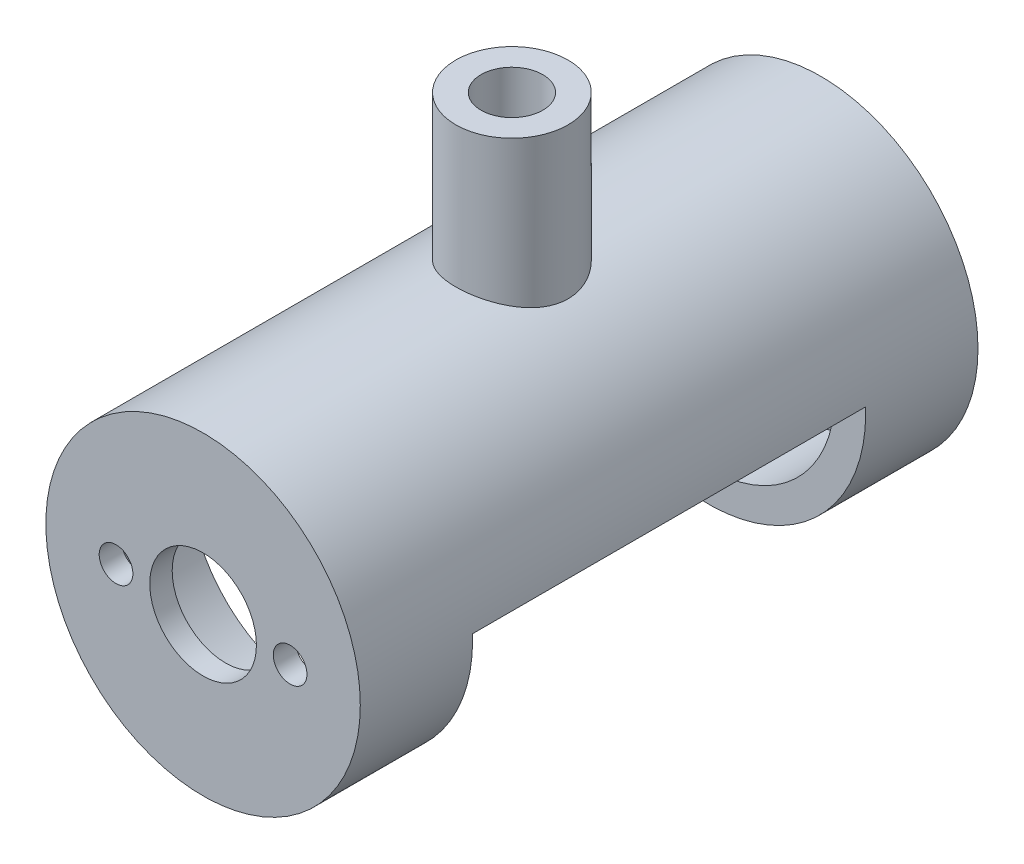
SolidWorks part; units mm, degrees
ref_plane "Alzado" through (0, 0, 0) normal (0, 0, 1) x (1, 0, 0)
ref_plane "Planta" through (0, 0, 0) normal (0, 1, 0) x (1, 0, 0)
ref_plane "Vista lateral" through (0, 0, 0) normal (1, 0, 0) x (0, 0, -1)
sketch "Croquis7" plane through (0, 0, 0) normal (0, 1, 0) x (1, 0, 0)
  circle A0 centre (0, 0) radius 5
  circle A1 centre (0, 0) radius 2.5
  dimension "D1" = 5
  dimension "D2" = 10
extrude "Saliente-Extruir7" add sketch "Croquis7" along normal blind 13
sketch "Croquis8" plane through (0, 0, 0) normal (0, 0, 1) x (1, 0, 0)
  circle A0 centre (0, -6.5) radius 6.5
  circle A1 centre (0, -6.5) radius 4
  dimension "D1" = 6.5
  dimension "D2" = 8
extrude "Saliente-Extruir8" add sketch "Croquis8" against normal blind 20 and the other way blind 20 separate body
sketch "Croquis9" plane through (0, 13, 0) normal (0, 1, 0) x (1, 0, 0)
  circle A0 centre (0, 0) radius 5
  circle A1 centre (0, 0) radius 2.5
extrude "Saliente-Extruir10" add sketch "Croquis9" against normal blind 16
sketch "Croquis10" plane through (0, 0, 20) normal (0, 0, 1) x (1, 0, 0)
  circle A0 centre (0, -6.5) radius 4
extrude "Cortar-Extruir1" cut sketch "Croquis10" against normal blind 43
sketch "Croquis11" plane through (0, 0, 20) normal (0, 0, 1) x (1, 0, 0)
  line L1 (-1, -9.2127) -> (1, -9.2127)
  line L2 (-1, -9.2127) -> (-1, -14.2827)
  line L3 (-1, -14.2827) -> (1, -14.2827)
  line L4 (1, -9.2127) -> (1, -14.2827)
  line L5 (-1, -9.2127) -> (1, -14.2827) construction
  line L6 (-1, -14.2827) -> (1, -9.2127) construction
  point P0 (0, -11.7477)
extrude "Cortar-Extruir2" cut sketch "Croquis11" against normal blind 43
sketch "Croquis12" plane through (0, 0, -20) normal (0, 0, -1) x (-1, 0, 0)
  line L1 (-1, -10.373) -> (-3.5, -10.373)
  line L2 (-1, -10.373) -> (-1, -18.923)
  line L3 (-1, -18.923) -> (-3.5, -18.923)
  line L4 (-3.5, -10.373) -> (-3.5, -18.923)
  dimension "D1" = 2.5
  dimension "D2" = 8.55
extrude "Saliente-Extruir11" add sketch "Croquis12" against normal blind 40
sketch "Croquis13" plane through (0, 0, -20) normal (0, 0, -1) x (-1, 0, 0)
  line L1 (1, -10.373) -> (3.5, -10.373)
  line L2 (1, -10.373) -> (1, -18.923)
  line L3 (1, -18.923) -> (3.5, -18.923)
  line L4 (3.5, -10.373) -> (3.5, -18.923)
  dimension "D1" = 2.5
  dimension "D2" = 8.55
extrude "Saliente-Extruir12" add sketch "Croquis13" against normal blind 40
sketch "Croquis14" plane through (-3.5, 0, 0) normal (-1, 0, 0) x (0, 0, 1)
  line L0 (-20, -18.923) -> (-20, -11.9772) construction
  line L1 (20, -18.923) -> (20, -11.9772) construction
  circle A0 centre (-13, -15.4501) radius 1.5
  circle A1 centre (0, -15.4501) radius 1.5
  circle A2 centre (13, -15.4501) radius 1.5
  dimension "D1" = 7
  dimension "D2" = 7
extrude "Cortar-Extruir3" cut sketch "Croquis14" against normal blind 40
sketch "Croquis15" plane through (0, 0, 20) normal (0, 0, 1) x (1, 0, 0)
  line L1 (-15.4538, 0) -> (9.6496, 0)
  line L2 (-15.4538, 0) -> (-15.4538, -20.0115)
  line L3 (-15.4538, -20.0115) -> (9.6496, -20.0115)
  line L4 (9.6496, 0) -> (9.6496, -20.0115)
extrude "Cortar-Extruir4" cut sketch "Croquis15" against normal blind 40
sketch "Croquis16" plane through (0, 0, 0) normal (0, 0, 1) x (1, 0, 0)
  line L0 (-5, 0) -> (5, 0) construction
  circle A0 centre (0, -13.5) radius 13.5
  circle A1 centre (0, -13.5) radius 11
  dimension "D1" = 13.5
extrude "Saliente-Extruir14" add sketch "Croquis16" against normal blind 55 and the other way blind 55 separate body
sketch "Croquis17" plane through (0, 13, 0) normal (0, 1, 0) x (1, 0, 0)
  circle A0 centre (0, 0) radius 2.5
  circle A1 centre (0, 0) radius 5
extrude "Saliente-Extruir15" add sketch "Croquis17" against normal blind 15
sketch "Croquis18" plane through (0, 0, -55) normal (0, 0, -1) x (-1, 0, 0)
  circle A0 centre (0, -13.5) radius 11
  circle A1 centre (0, -13.5) radius 4.25
extrude "Saliente-Extruir16" add sketch "Croquis18" against normal blind 3
sketch "Croquis20" plane through (0, 0, -55) normal (0, 0, -1) x (-1, 0, 0)
  circle A0 centre (-7.75, -13.5) radius 1.5
  circle A1 centre (7.75, -13.5) radius 1.5
  circle A2 centre (0, -13.5) radius 4.25 construction
  dimension "D1" = 7.75
  dimension "D2" = 7.75
extrude "Cortar-Extruir5" cut sketch "Croquis20" against normal blind 3
sketch "Croquis21" plane through (0, 0, 55) normal (0, 0, 1) x (1, 0, 0)
  circle A0 centre (0, -13.5) radius 11
  circle A1 centre (0, -13.5) radius 4.25
  circle A2 centre (7.75, -13.5) radius 1.5
  circle A3 centre (-7.75, -13.5) radius 1.3863
extrude "Saliente-Extruir17" add sketch "Croquis21" against normal blind 3
sketch "Croquis22" plane through (0, 0, 0) normal (1, 0, 0) x (0, 0, -1)
  line L0 (-55, -27) -> (55, -27) construction
  line L1 (-45, -27) -> (45, -27)
  line L2 (-45, -27) -> (-45, -13)
  line L3 (-45, -13) -> (45, -13)
  line L4 (45, -27) -> (45, -13)
  line L5 (-55, 0) -> (-55, -27) construction
  line L6 (55, -27) -> (55, 0) construction
  dimension "D1" = 10
  dimension "D2" = 10
  dimension "D3" = 14
extrude "Cortar-Extruir6" cut sketch "Croquis22" against normal blind 18 and the other way blind 31
sketch "Croquis24" plane through (0, 0, 55) normal (0, 0, 1) x (1, 0, 0)
  circle A0 centre (0, -13.5) radius 13.5
extrude "Cortar-Extruir7" cut sketch "Croquis24" against normal blind 27.5
sketch "Croquis27" plane through (0, 0, 27.5) normal (0, 0, 1) x (1, 0, 0)
  circle A0 centre (0, -13.5) radius 13.5
  circle A1 centre (0, -13.5) radius 11
extrude "Saliente-Extruir19" add sketch "Croquis27" against normal blind 10
sketch "Croquis28" plane through (0, 0, 27.5) normal (0, 0, 1) x (1, 0, 0)
  circle A0 centre (0, -13.5) radius 11
  circle A1 centre (-7.75, -13.5) radius 1.5
  circle A2 centre (7.75, -13.5) radius 1.5
  circle A3 centre (0, -13.5) radius 4.25
extrude "Saliente-Extruir20" add sketch "Croquis28" against normal blind 3
sketch "Croquis29" plane through (0, 0, -55) normal (0, 0, -1) x (-1, 0, 0)
  circle A0 centre (0, -13.5) radius 13.5
extrude "Cortar-Extruir8" cut sketch "Croquis29" against normal blind 27.5
sketch "Croquis30" plane through (0, 0, -27.5) normal (0, 0, -1) x (-1, 0, 0)
  circle A0 centre (0, -13.5) radius 13.5
  circle A1 centre (0, -13.5) radius 11
extrude "Saliente-Extruir21" add sketch "Croquis30" against normal blind 10
sketch "Croquis31" plane through (0, 0, -27.5) normal (0, 0, -1) x (-1, 0, 0)
  circle A0 centre (0, -13.5) radius 11
  circle A1 centre (0, -13.5) radius 4.25
  circle A2 centre (7.75, -13.5) radius 1.5
  circle A3 centre (-7.75, -13.5) radius 1.5
extrude "Saliente-Extruir22" add sketch "Croquis31" against normal blind 3
sketch "Croquis32" plane through (0, 0, 27.5) normal (0, 0, 1) x (1, 0, 0)
  circle A0 centre (0, -13.5) radius 14
  circle A1 centre (0, -13.5) radius 13.5
extrude "Saliente-Extruir25" add sketch "Croquis32" against normal blind 10
sketch "Croquis35" plane through (0, 0, -27.5) normal (0, 0, -1) x (-1, 0, 0)
  circle A0 centre (0, -13.5) radius 13.5
  circle A1 centre (0, -13.5) radius 14
extrude "Saliente-Extruir26" add sketch "Croquis35" against normal blind 10
sketch "Croquis36" plane through (0, 0, -27.5) normal (0, 0, -1) x (-1, 0, 0)
  line L0 (-14, -13.5) -> (-13.5, -13.5)
  line L1 (13.5, -13.5) -> (14, -13.5)
  arc A0 (-14, -13.5) -> (14, -13.5) centre (0, -13.5) cw
  circle A1 centre (0, -13.5) radius 14 construction
  arc A2 (-13.5, -13.5) -> (13.5, -13.5) centre (0, -13.5) cw
  dimension "D1" = 0.5
  dimension "D2" = 0.5
extrude "Saliente-Extruir27" add sketch "Croquis36" against normal blind 47
sketch "Croquis37" plane through (0, 0, 17.5) normal (0, 0, -1) x (-1, 0, 0)
  circle A0 centre (0, -13.5) radius 11.75
  dimension "D1" = 23.5
extrude "Cortar-Extruir9" cut sketch "Croquis37" along normal blind 43 and the other way blind 8
sketch "Croquis38" plane through (0, 13, 0) normal (0, 1, 0) x (1, 0, 0)
  circle A0 centre (0, 0) radius 2.75
  circle A1 centre (0, 0) radius 2.5
extrude "Cortar-Extruir10" cut sketch "Croquis38" against normal blind 12
sketch "Croquis39" plane through (0, 0, 27.5) normal (0, 0, 1) x (1, 0, 0)
  circle A0 centre (0, -13.5) radius 4.75
  dimension "D1" = 9.5
extrude "Cortar-Extruir11" cut sketch "Croquis39" against normal blind 64
sketch "Croquis41" plane through (0, 0, -17.5) normal (0, 0, 1) x (1, 0, 0)
  circle A0 centre (0, -13.5) radius 11.75
  circle A1 centre (0, -13.5) radius 11.125
extrude "Saliente-Extruir28" add sketch "Croquis41" against normal up to surface (10 mm away) up to face at (-4.75, -13.5, -27.5)
sketch "Croquis42" plane through (0, 0, 17.5) normal (0, 0, -1) x (-1, 0, 0)
  circle A0 centre (0, -13.5) radius 11.75
  circle A1 centre (0, -13.5) radius 11.125
extrude "Saliente-Extruir29" add sketch "Croquis42" against normal up to surface (10 mm away) up to face at (4.75, -13.5, 27.5)
sketch "Croquis43" plane through (0, 0, 17.5) normal (0, 0, -1) x (-1, 0, 0)
  circle A0 centre (0, -13.5) radius 11.125
  circle A1 centre (0, -13.5) radius 11
extrude "Saliente-Extruir30" add sketch "Croquis43" against normal up to surface (10 mm away) up to face at (14, -13.5, 27.5)
sketch "Croquis45" plane through (0, 0, -17.5) normal (0, 0, 1) x (1, 0, 0)
  circle A0 centre (0, -13.5) radius 11.125
  circle A1 centre (0, -13.5) radius 11
extrude "Saliente-Extruir31" add sketch "Croquis45" against normal up to surface (10 mm away) up to face at (-14, -13.5, -27.5)
sketch "Croquis46" plane through (0, -13, 0) normal (0, -1, 0) x (-1, 0, 0)
  line L1 (11.7394, -17.5) -> (20.8059, -17.5)
  line L2 (11.7394, -17.5) -> (11.7394, 17.5)
  line L3 (11.7394, 17.5) -> (20.8059, 17.5)
  line L4 (20.8059, -17.5) -> (20.8059, 17.5)
  line L5 (-11.7394, 17.5) -> (-15.7794, 17.5)
  line L6 (-11.7394, 17.5) -> (-11.7394, -17.5)
  line L7 (-11.7394, -17.5) -> (-15.7794, -17.5)
  line L8 (-15.7794, 17.5) -> (-15.7794, -17.5)
extrude "Cortar-Extruir12" cut sketch "Croquis46" along normal blind 11
sketch "Croquis47" plane through (0, 0, 17.5) normal (0, 0, -1) x (-1, 0, 0)
  circle A0 centre (0, -13.5) radius 11.25
extrude "Cortar-Extruir13" cut sketch "Croquis47" against normal up to surface (8 mm away) up to face at (-4.75, -13.5, 25.5)
sketch "Croquis48" plane through (0, 0, -17.5) normal (0, 0, 1) x (1, 0, 0)
  circle A0 centre (0, -13.5) radius 11.25
extrude "Cortar-Extruir14" cut sketch "Croquis48" against normal up to surface (8 mm away) up to face at (-4.75, -13.5, -25.5)
